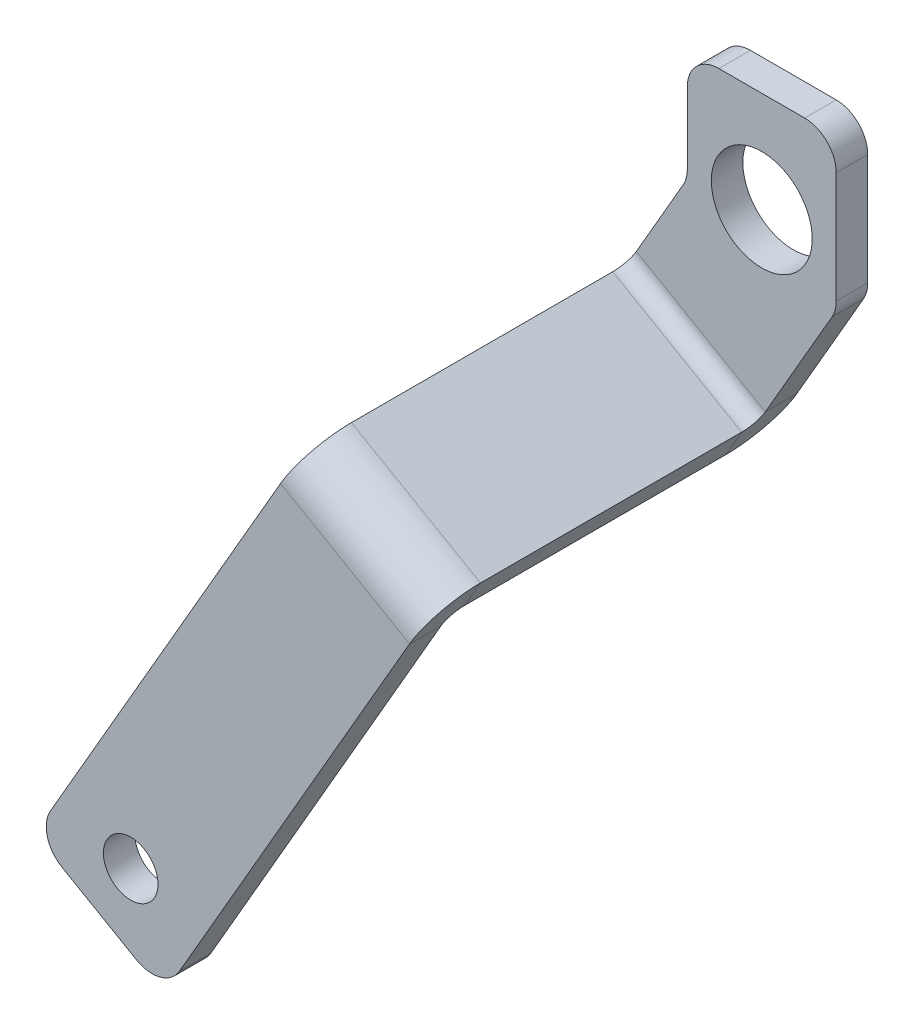
SolidWorks part; units mm, degrees
note: The reader was unsure of these and kept them because the rebuilt part matched: thickness of "Base-Flange1", "Edge-Flange1", "Edge-Flange2"; flange length of "Edge-Flange1", "Edge-Flange2".
material "3003-H14"
ref_plane "X-Y Datum" through (0, 0, 0) normal (0, 0, 1) x (1, 0, 0)
ref_plane "X-Z Datum" through (0, 0, 0) normal (0, 1, 0) x (1, 0, 0)
ref_plane "Y-Z Datum" through (0, 0, 0) normal (1, 0, 0) x (0, 0, -1)
sketch "Sketch2" plane through (0, 0, 0) normal (0, 0, 1) x (1, 0, 0)
  line L0 (-136.8621, 27.1278) -> (-149.8525, 34.6278) construction
  line L4 (-136.8621, 27.1278) -> (-140.0371, 21.6286)
  line L5 (-140.0371, 21.6286) -> (-153.0275, 29.1286)
  line L6 (-153.0275, 29.1286) -> (-149.8525, 34.6278)
  line L7 (-136.8621, 27.1278) -> (-115.2721, 64.5228)
  line L8 (-154.0481, 28.0608) -> (-140.4515, 20.2108) construction
  line L9 (-154.0481, 28.0608) -> (-140.4515, 20.2108) construction
  line L10 (-115.2721, 64.5228) -> (-128.2625, 72.0228)
  line L11 (-128.2625, 72.0228) -> (-149.8525, 34.6278)
  circle A0 centre (-143.3573, 30.8778) radius 2.5 construction
  circle A1 centre (-143.3573, 30.8778) radius 2.5 construction
  circle A2 centre (-143.3573, 30.8778) radius 5.08 construction
  point P6 (-143.3573, 30.8778)
  dimension "D2" = 10.16
  dimension "D1" = 15
  dimension "D3" = 6.35
  dimension "D4" = 43.18
base flange "Base-Flange1" sketch "Sketch2" thickness 3.175 reverse thickness direction yes parameters "D1"=10
edge flange "Edge-Flange1" sketch "Sketch11" flange angle 90 flange length 31.075 flange position bend outside bend radius 1.5875 thickness 3.175 relief rectangular parameters "D6"=0
sketch "Sketch11" plane through (-0.8788, -1.5222, 0) normal (0.5, 0.866, 0) x (0.866, -0.5, 0)
  line L0 (-132.0899, 0) -> (-147.0899, 0) construction
  line L1 (-132.0899, 0) -> (-147.0899, 0)
  line L2 (-147.0899, 0) -> (-147.0899, 27.9)
  line L3 (-147.0899, 27.9) -> (-132.0899, 27.9)
  line L4 (-132.0899, 27.9) -> (-132.0899, 0)
bend "EdgeBend1" bend radius 1.5875 bend angle 90 parameters "D5"=1
edge flange "Edge-Flange2" sketch "Sketch14" flange angle 90 flange length 9.525 flange position bend outside bend radius 1.5875 thickness 3.175 relief rectangular parameters "D6"=0
sketch "Sketch14" plane through (1.5024, 2.6023, -27.9) normal (0, 0, -1) x (-0.866, 0.5, 0)
  line L2 (132.0899, 0) -> (132.0899, 6.35)
  line L3 (132.0899, 6.35) -> (147.0899, 6.35)
  line L4 (147.0899, 6.35) -> (147.0899, 0)
  line L7 (132.0899, 0) -> (147.0899, 0) construction
  line L8 (132.0899, 0) -> (147.0899, 0)
bend "EdgeBend2" bend radius 1.5875 bend angle 90 parameters "D5"=2
sketch "Sketch15" plane through (0, 0, -32.6625) normal (0, 0, -1) x (-1, 0, 0)
  line L0 (122.7062, 81.6465) -> (109.7158, 74.1465) construction
  line L1 (122.7062, 81.6465) -> (109.7158, 74.1465)
  line L2 (119.9533, 97.6354) -> (104.9533, 97.6354)
  line L3 (109.7158, 74.1465) -> (104.9533, 82.3954)
  line L4 (104.9533, 82.3954) -> (104.9533, 97.6354)
  line L5 (119.9533, 97.6354) -> (119.9533, 86.4146)
  line L6 (119.9533, 86.4146) -> (122.7062, 81.6465)
  circle A0 centre (112.4533, 87.4754) radius 5.08
  point P5 (112.4533, 97.6354)
  dimension "D4" = 10.16
  dimension "D1" = 15
  dimension "D2" = 15.24
  dimension "D3" = 9.525
extrude "Boss-Extrude1" add sketch "Sketch15" against normal blind 3.175
hole_wizard "M5 Clearance Hole1" positions "Sketch16" profile "Sketch17" hole size "M5" standard "ANSI Metric" end condition through all
sketch "Sketch16" plane through (0, 0, 3.175) normal (0, 0, 1) x (1, 0, 0)
  point P0 (-143.3573, 30.8778)
sketch "Sketch17" plane through (-143.3573, 30.8778, 3.175) normal (1, 0, 0) x (0, -1, 0)
  line L0 (0, 0) -> (0, 35.8375)
  line L1 (0, 35.8375) -> (2.75, 35.8375)
  line L2 (2.75, 35.8375) -> (2.75, 0)
  line L5 (2.75, 0) -> (0, 0)
  line L11 (0, -6.35) -> (0, 107.95) construction
  dimension "Thru Hole Dia." = 5.5
  dimension "Thru Hole Depth" = 35.8375
fillet "Fillet1" radius 3.175 6 edges at (-104.9533, 82.3954, -31.075) (-119.9533, 86.4146, -31.075) (-119.9533, 97.6354, -31.075) (-104.9533, 97.6354, -31.075) (-140.0371, 21.6286, 1.5875) (-153.0275, 29.1286, 1.5875)
sketch "Bend-Lines1" [suppressed] plane through (0, 0, 0) normal (0, 1, 0) x (1, 0, 0)
sketch "Bounding-Box1" [suppressed] plane through (0, 0, 0) normal (0, 1, 0) x (1, 0, 0)
sheet metal parameters "Sheet-Metal1" thickness 3.175 parameters "D1"=10
flat pattern "Flat-Pattern1" [suppressed]
sketch "Bend-Lines2" plane through (0, 0, 0) normal (0, 1, 0) x (1, 0, 0)
sketch3d "Bounding-Box2" [suppressed]
  line L0 (139.8145, 21.6286, 0) -> (127.1145, 43.6256, 0) construction
  line L1 (152.8049, 29.1286, 0) -> (140.1049, 51.1256, 0) construction
  line L2 (139.8145, 21.6286, 0) -> (152.8049, 29.1286, 0) construction
  line L3 (127.1145, 43.6256, 0) -> (140.1049, 51.1256, 0) construction
sheet metal parameters "Sheet-Metal2" thickness 3.175 parameters "D1"=10
flat pattern "Flat-Pattern1"
sketch "Bend-Lines2" plane through (0, 0, 0) normal (0, 0, -1) x (-1, 0, 0)
  line L0 (138.858, 53.2852) -> (125.8677, 45.7852) construction
  line L1 (138.858, 53.2852) -> (125.8677, 45.7852) construction
sketch3d "Bounding-Box2" [suppressed]
  line L0 (139.8145, 21.6286, 0) -> (107.9521, 76.8158, 0) construction
  line L1 (152.8049, 29.1286, 0) -> (120.9425, 84.3158, 0) construction
  line L2 (139.8145, 21.6286, 0) -> (152.8049, 29.1286, 0) construction
  line L3 (107.9521, 76.8158, 0) -> (120.9425, 84.3158, 0) construction
bend of the flat pattern "Flatten-<EdgeBend1>1"
sheet metal parameters "Sheet-Metal3" thickness 3.175 parameters "D1"=10
flat pattern "Flat-Pattern1"
sketch "Bend-Lines2" plane through (0, 0, 0) normal (0, 0, -1) x (-1, 0, 0)
  line L0 (138.858, 53.2852) -> (125.8677, 45.7852) construction
  line L1 (138.858, 53.2852) -> (125.8677, 45.7852) construction
  line L2 (120.0332, 85.8908) -> (107.0428, 78.3908) construction
  line L3 (120.0332, 85.8908) -> (107.0428, 78.3908) construction
sketch3d "Bounding-Box2" [suppressed]
  line L0 (139.8145, 21.6286, 0) -> (101.8272, 87.4245, 0) construction
  line L1 (152.8049, 29.1286, 0) -> (114.8176, 94.9245, 0) construction
  line L2 (139.8145, 21.6286, 0) -> (152.8049, 29.1286, 0) construction
  line L3 (101.8272, 87.4245, 0) -> (114.8176, 94.9245, 0) construction
bend of the flat pattern "Flatten-<EdgeBend1>1"
bend of the flat pattern "Flatten-<EdgeBend2>1"
sheet metal parameters "Sheet-Metal4" thickness 3.175 parameters "D1"=10
flat pattern "Flat-Pattern1"
sketch "Bend-Lines2" plane through (0, 0, 0) normal (0, 0, -1) x (-1, 0, 0)
  line L0 (137.4931, 56.0348) -> (124.5028, 48.5348) construction
  line L1 (137.4931, 56.0348) -> (124.5028, 48.5348) construction
  line L2 (118.6682, 88.6405) -> (105.6779, 81.1405) construction
  line L3 (118.6682, 88.6405) -> (105.6779, 81.1405) construction
sketch3d "Bounding-Box2" [suppressed]
  line L0 (135.3379, 19.2877, 0) -> (91.205, 107.8835, 0) construction
  line L1 (153.4381, 28.3041, 0) -> (109.3052, 116.8999, 0) construction
  line L2 (135.3379, 19.2877, 0) -> (153.4381, 28.3041, 0) construction
  line L3 (91.205, 107.8835, 0) -> (109.3052, 116.8999, 0) construction
bend of the flat pattern "Flatten-<EdgeBend1>1"
bend of the flat pattern "Flatten-<EdgeBend2>1"
sheet metal parameters "Sheet-Metal5" thickness 3.175 parameters "D1"=10
flat pattern "Flat-Pattern1"
sketch "Bend-Lines2" plane through (0, 0, 0) normal (0, 0, -1) x (-1, 0, 0)
  line L0 (127.0156, 74.1824) -> (114.0253, 66.6824) construction
  line L1 (127.0156, 74.1824) -> (114.0253, 66.6824) construction
  line L2 (111.3657, 101.2888) -> (98.3754, 93.7888) construction
  line L3 (111.3657, 101.2888) -> (98.3754, 93.7888) construction
sketch3d "Bounding-Box2" [suppressed]
  line L0 (136.115, 19.7415, 0) -> (84.2859, 119.3482, 0) construction
  line L1 (153.1468, 28.6038, 0) -> (101.3178, 128.2105, 0) construction
  line L2 (136.115, 19.7415, 0) -> (153.1468, 28.6038, 0) construction
  line L3 (84.2859, 119.3482, 0) -> (101.3178, 128.2105, 0) construction
bend of the flat pattern "Flatten-<EdgeBend1>1"
bend of the flat pattern "Flatten-<EdgeBend2>1"
